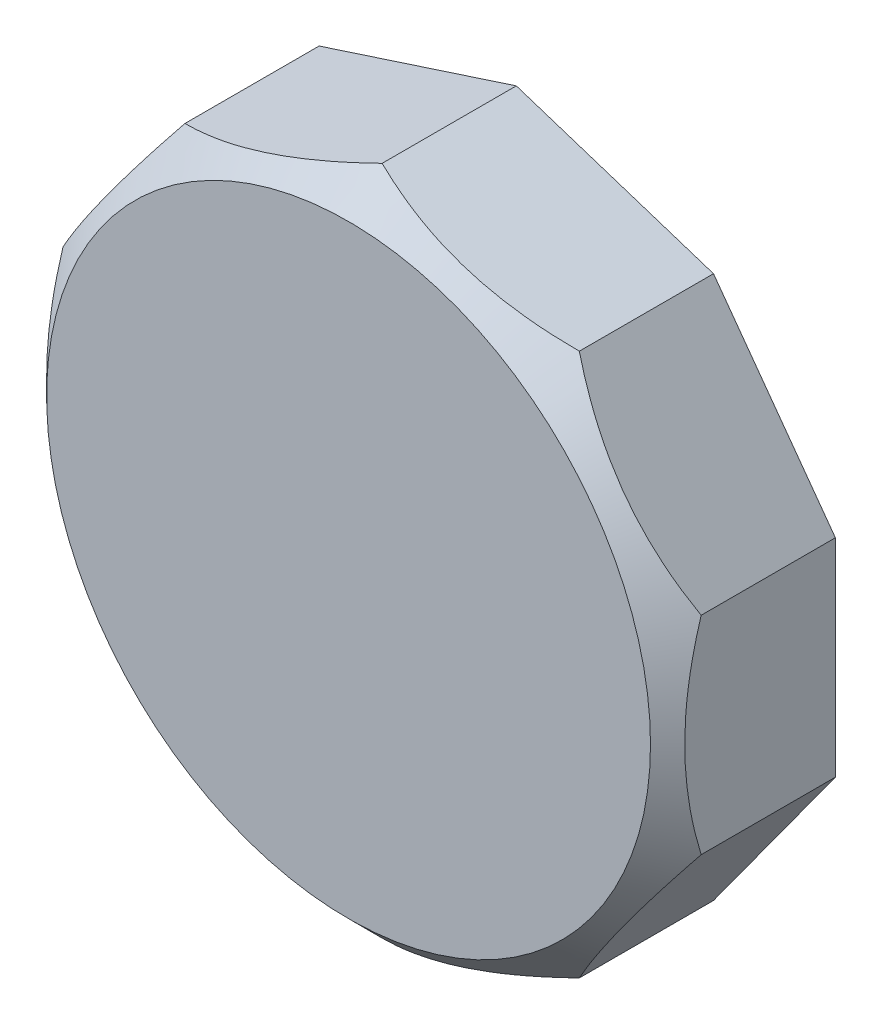
SolidWorks part; units mm, degrees
ref_plane "Front Plane" through (0, 0, 0) normal (1, 0, 0) x (0, 1, 0)
ref_plane "Top Plane" through (0, 0, 0) normal (0, 0, 1) x (0, 1, 0)
ref_plane "Right Plane" through (0, 0, 0) normal (0, 1, 0) x (-1, 0, 0)
sketch "Sketch1" plane through (0, 0, 0) normal (0, 0, 1) x (0, 1, 0)
  circle A0 centre (0, 0) radius 50
  dimension "D1" = 100
extrude "Boss-Extrude1" add sketch "Sketch1" along normal blind 25
sketch "Sketch2" plane through (0, 0, 0) normal (0, 0, -1) x (1, 0, 0)
  circle A0 centre (0, 0) radius 40
  dimension "D1" = 80
extrude "Cut-Extrude1" cut sketch "Sketch2" against normal blind 20
ref_plane "Plane1" through (0, 0, 16.25) normal (0, 0, -1) x (-1, 0, 0)
sketch "Sketch3" plane through (0, 0, 16.25) normal (0, 0, -1) x (-1, 0, 0)
  circle A0 centre (0, 0) radius 40 construction
  circle A1 centre (0, 0) radius 40
curve "Helix/Spiral1" pitch 12.5 height 25 radius 40 centre (0, 0, 16.25) axis (0, 0, -1) start towards (1, 0, 0)
sketch "Sketch5" plane through (0, 0, 0) normal (0, 1, 0) x (-1, 0, 0)
  line L0 (-44, 16.25) -> (44, 16.25) construction
  line L2 (-44, 12.25) -> (-36, 12.25)
  line L3 (-44, 12.25) -> (-44, 20.25)
  line L4 (-44, 20.25) -> (-36, 20.25)
  line L5 (-36, 12.25) -> (-36, 20.25)
  line L6 (-44, 12.25) -> (-36, 20.25) construction
  line L7 (-44, 20.25) -> (-36, 12.25) construction
  circle A0 centre (-40, 16.25) radius 4 construction
  spline S0 degree 3 poles (-40, 16.25) (-40, 16.1015) (-39.3258, 15.8034) (-36.3425, 15.3572) (-31.5368, 14.9107) (-25.1498, 14.4643) (-17.5016, 14.0179) (-6.1339, 13.4226) (6.1339, 12.8274) (17.5016, 12.2321) (25.1498, 11.7857) (31.5368, 11.3393) (36.3425, 10.8929) (39.3258, 10.4464) (40.3371, 10) (39.3258, 9.5536) (36.3425, 9.1071) (31.5368, 8.6607) (25.1498, 8.2143) (17.5016, 7.7679) (6.1339, 7.1726) (-6.1339, 6.5774) (-17.5016, 5.9821) (-25.1498, 5.5357) (-31.5368, 5.0893) (-36.3425, 4.6429) (-39.3258, 4.1964) (-40.3371, 3.75) (-39.3258, 3.3036) (-36.3425, 2.8571) (-31.5368, 2.4107) (-25.1498, 1.9643) (-17.5016, 1.5179) (-6.1339, 0.9226) (6.1339, 0.3274) (17.5016, -0.2679) (25.1498, -0.7143) (31.5368, -1.1607) (36.3425, -1.6071) (39.3258, -2.0536) (40.3371, -2.5) (39.3258, -2.9464) (36.3425, -3.3929) (31.5368, -3.8393) (25.1498, -4.2857) (17.5016, -4.7321) (6.1339, -5.3274) (-6.1339, -5.9226) (-17.5016, -6.5179) (-25.1498, -6.9643) (-31.5368, -7.4107) (-36.3425, -7.8572) (-39.3258, -8.3034) (-40, -8.6015) (-40, -8.75) knots 0 0 0 0 0.017857 0.035714 0.053571 0.071429 0.089286 0.107143 0.142857 0.160714 0.178571 0.196429 0.214286 0.232143 0.25 0.267857 0.285714 0.303571 0.321429 0.339286 0.357143 0.392857 0.410714 0.428571 0.446429 0.464286 0.482143 0.5 0.517857 0.535714 0.553571 0.571429 0.589286 0.607143 0.642857 0.660714 0.678571 0.696429 0.714286 0.732143 0.75 0.767857 0.785714 0.803571 0.821429 0.839286 0.857143 0.892857 0.910714 0.928571 0.946429 0.964286 0.982143 1 1 1 1 construction
  dimension "D1" = 8
sweep "Cut-Sweep2" cut profiles "Sketch5" path "Helix/Spiral1" align with end faces yes
chamfer "Chamfer2" distance 5 angle 45 1 edges at (50, 0, 25)
sketch "Sketch6" plane through (0, 0, 0) normal (0, 0, -1) x (1, 0, 0)
  circle A0 centre (0, 0) radius 41
  circle A1 centre (0, 0) radius 40 construction
  dimension "D1" = 1
extrude "Cut-Extrude2" cut sketch "Sketch6" against normal blind 20.5
sketch "Sketch7" plane through (0, 0, 25) normal (0, 0, 1) x (1, 0, 0)
  line L1 (-0.75, 49.25) -> (0.75, 49.25)
  line L2 (-0.75, 49.25) -> (-0.75, 50.75)
  line L3 (-0.75, 50.75) -> (0.75, 50.75)
  line L4 (0.75, 49.25) -> (0.75, 50.75)
  line L5 (-0.75, 49.25) -> (0.75, 50.75) construction
  line L6 (-0.75, 50.75) -> (0.75, 49.25) construction
  circle A0 centre (0, 0) radius 50 construction
  point P0 (0, 50)
  dimension "D1" = 1.5
  dimension "D2" = 1.5
extrude "Cut-Extrude3" [suppressed] cut sketch "Sketch7" against normal through all
pattern_circular "CirPattern1" [suppressed] count 100 over 360 of bodies 106
sketch "Sketch9" plane through (0, 0, 25) normal (0, 0, 1) x (1, 0, 0)
  line L1 (0, 50) -> (-29.3893, 40.4508)
  line L2 (-29.3893, 40.4508) -> (-47.5528, 15.4508)
  line L3 (-47.5528, 15.4508) -> (-47.5528, -15.4508)
  line L4 (-47.5528, -15.4508) -> (-29.3893, -40.4508)
  line L5 (-29.3893, -40.4508) -> (0, -50)
  line L6 (0, -50) -> (29.3893, -40.4508)
  line L7 (29.3893, -40.4508) -> (47.5528, -15.4508)
  line L8 (47.5528, -15.4508) -> (47.5528, 15.4508)
  line L9 (47.5528, 15.4508) -> (29.3893, 40.4508)
  line L10 (29.3893, 40.4508) -> (0, 50)
  circle A0 centre (0, 0) radius 47.5528 construction
  circle A1 centre (0, 0) radius 50 construction
extrude "Cut-Extrude4" cut sketch "Sketch9" against normal through all flip side to cut
scale "Scale1" scale about origin uniform scaling yes scale factor 0.78
